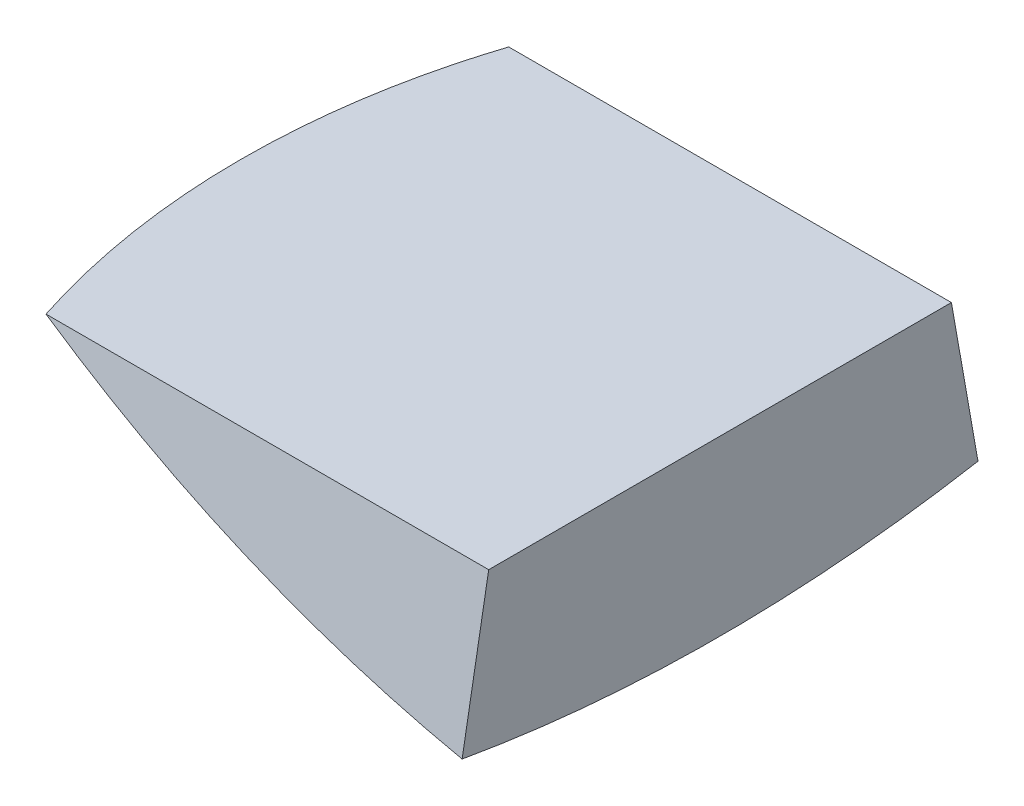
SolidWorks part; units mm, degrees
material "Polyurethane Foam Rigid"
ref_plane "Front Plane" through (0, 0, 0) normal (0, 0, 1) x (1, 0, 0)
ref_plane "Top Plane" through (0, 0, 0) normal (0, 1, 0) x (1, 0, 0)
ref_plane "Right Plane" through (0, 0, 0) normal (1, 0, 0) x (0, 0, -1)
sketch "Sketch1" plane through (0, 0, 0) normal (0, 0, 1) x (1, 0, 0)
  line L0 (-132.3199, -750.4235) -> (-132.3199, -648.8235)
  line L1 (0, 0) -> (0, -17.1989) construction
  line L2 (0, 0) -> (0, -324.9103) construction
  line L3 (0, 0) -> (-132.3199, -750.4235) construction
  line L4 (-132.3199, -648.8235) -> (-399.5899, -648.8235)
  line L5 (0, 0) -> (-376.3803, 0) construction
  line L6 (0, 11.5765) -> (-387.6987, 11.5765) construction
  arc A0 (-132.3199, -750.4235) -> (-399.5899, -648.8235) centre (0, 0) cw
  dimension "D2" = 762
  dimension "D1" = 10
  dimension "D3" = 101.6
  dimension "D4" = 762
revolve "Revolve1" add sketch "Sketch1" angle 20 mid plane about L6
sketch "Sketch2" plane through (-132.3199, 0, 0) normal (1, 0, 0) x (0, 0, -1)
  line L1 (-217.2973, -505.5801) -> (197.3972, -505.5801)
  line L2 (-217.2973, -505.5801) -> (-217.2973, -661.5235)
  line L3 (-217.2973, -661.5235) -> (197.3972, -661.5235)
  line L4 (197.3972, -505.5801) -> (197.3972, -661.5235)
  arc A1 (-132.3199, -738.847) -> (132.3199, -738.847) centre (0, 11.5765) ccw construction
  point P4 (0, -750.4235)
  dimension "D1" = 88.9
extrude "Cut-Extrude1" cut sketch "Sketch2" against normal through all
equation "\"gapAngle\" = 10deg"
equation "\"D1@Sketch1\"=\"gapAngle\""
equation "\"LegFront\" = 30in"
equation "\"D2@Sketch1\"=\"LegFront\""
equation "\"LegSide\" = 30in"
equation "\"D4@Sketch1\"=\"LegSide\""
